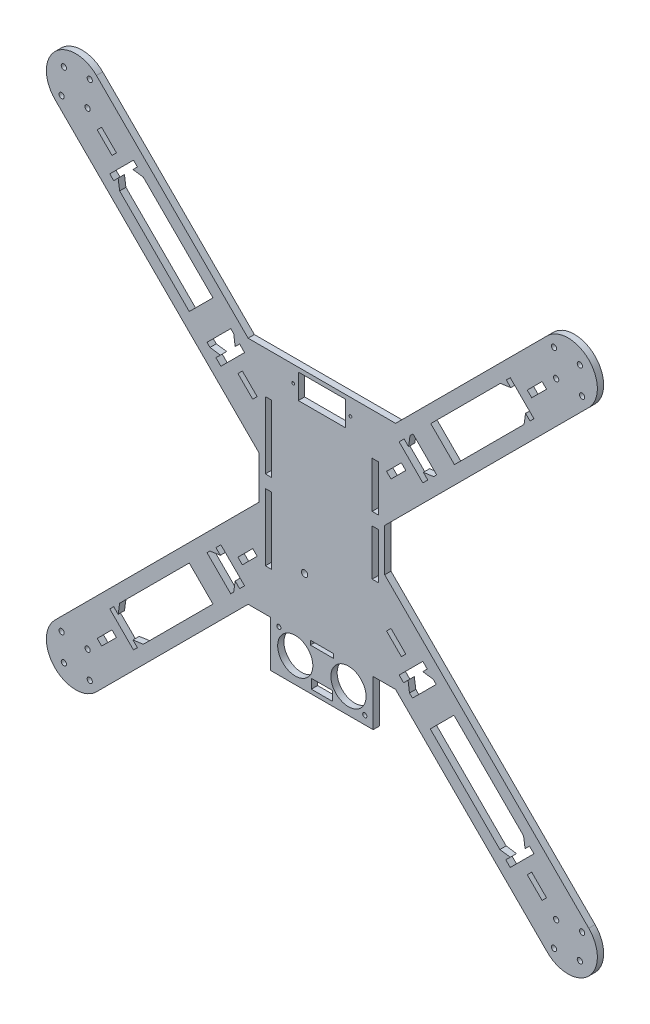
SolidWorks part; units mm, degrees
material "Custom Plastic"
ref_plane "Front Plane" through (0, 0, 0) normal (0, 0, 1) x (1, 0, 0)
ref_plane "Top Plane" through (0, 0, 0) normal (0, 1, 0) x (1, 0, 0)
ref_plane "Right Plane" through (0, 0, 0) normal (1, 0, 0) x (0, 0, -1)
sketch "Sketch1" plane through (0, 0, 0) normal (0, 0, 1) x (1, 0, 0)
  line L0 (117.5, 117.5) -> (-117.5, 117.5) construction
  line L1 (-117.5, 117.5) -> (117.5, -117.5) construction
  line L2 (117.5, -117.5) -> (-117.5, -117.5) construction
  line L3 (-117.5, -117.5) -> (117.5, 117.5) construction
  line L4 (117.5, 117.5) -> (117.5, -117.5) construction
  line L5 (-117.5, 117.5) -> (-117.5, -117.5) construction
  line L6 (0, 117.5) -> (0, -117.5) construction
  line L7 (35.201, 55) -> (-35.201, 55)
  line L8 (-30, 55) -> (30, 55) construction
  line L9 (-35.201, 55) -> (-107.6005, 127.3995)
  line L10 (-127.3995, 107.6005) -> (-30, 10.201)
  line L11 (-117.5, 0) -> (117.5, 0) construction
  line L12 (-30, 10.201) -> (-30, -10.201)
  line L13 (30, 55) -> (30, -55) construction
  line L14 (30, -55) -> (-30, -55) construction
  line L15 (-30, -55) -> (-30, 55) construction
  line L16 (30, 55) -> (-30, -55) construction
  line L17 (-24.5, -55) -> (-24.5, -77)
  line L18 (-127.3995, -107.6005) -> (-30, -10.201)
  line L19 (-24.5, -77) -> (24.5, -77)
  line L20 (-35.201, -55) -> (-107.6005, -127.3995)
  line L21 (35.201, -55) -> (24.5, -55)
  line L22 (35.201, -55) -> (107.6005, -127.3995)
  line L23 (127.3995, -107.6005) -> (30, -10.201)
  line L24 (30, 10.201) -> (30, -10.201)
  line L25 (127.3995, 107.6005) -> (30, 10.201)
  line L26 (35.201, 55) -> (107.6005, 127.3995)
  line L27 (24.5, -55) -> (24.5, -77)
  line L28 (-24.5, -55) -> (-35.201, -55)
  arc A0 (-107.6005, 127.3995) -> (-127.3995, 107.6005) centre (-117.5, 117.5) ccw
  arc A12 (-107.6005, -127.3995) -> (-127.3995, -107.6005) centre (-117.5, -117.5) cw
  arc A16 (107.6005, -127.3995) -> (127.3995, -107.6005) centre (117.5, -117.5) ccw
  arc A24 (107.6005, 127.3995) -> (127.3995, 107.6005) centre (117.5, 117.5) cw
  point P3 (0, 0)
  point P18 (0, 0)
  point P21 (0, -77)
  point P33 (-117.5, 117.5)
  point P34 (-30, 0)
  point P65 (0, -55)
  point P80 (0, 55)
  dimension "D3" = 14
  dimension "D8" = 24.5
  dimension "D7" = 22
  dimension "D1" = 235
  dimension "D2" = 235
  dimension "D4" = 60
  dimension "D5" = 110
  dimension "D6" = 28
extrude "Boss-Extrude1" add sketch "Sketch1" against normal blind 3
sketch "Sketch4" plane through (0, 0, 0) normal (0, 0, 1) x (1, 0, 0)
  line L0 (0, 0) -> (0, 55) construction
  line L1 (35.201, 55) -> (-35.201, 55) construction
  line L2 (0, 0) -> (-30, 0) construction
  line L3 (-30, 10.201) -> (-30, -10.201) construction
  line L4 (-30, 0) -> (-30, 10.201) construction
  line L5 (-30, 10.201) -> (-127.3995, 107.6005) construction
  line L6 (-35.201, 55) -> (-107.6005, 127.3995) construction
  line L7 (-107.6005, 127.3995) -> (-127.3995, 107.6005) construction
  line L8 (-110.7825, 124.2175) -> (-124.2175, 110.7825) construction
  line L9 (-123.1569, 123.1569) -> (-111.8431, 111.8431) construction
  circle A20 centre (-110.7825, 124.2175) radius 1.25
  circle A21 centre (-124.2175, 110.7825) radius 1.25
  circle A22 centre (-123.1569, 123.1569) radius 1.25
  circle A23 centre (-111.8431, 111.8431) radius 1.25
  circle A24 centre (111.8431, 111.8431) radius 1.25
  circle A25 centre (110.7825, 124.2175) radius 1.25
  circle A26 centre (123.1569, 123.1569) radius 1.25
  circle A27 centre (124.2175, 110.7825) radius 1.25
  circle A28 centre (111.8431, -111.8431) radius 1.25
  circle A29 centre (124.2175, -110.7825) radius 1.25
  circle A30 centre (123.1569, -123.1569) radius 1.25
  circle A31 centre (110.7825, -124.2175) radius 1.25
  circle A32 centre (-111.8431, -111.8431) radius 1.25
  circle A33 centre (-110.7825, -124.2175) radius 1.25
  circle A34 centre (-123.1569, -123.1569) radius 1.25
  circle A35 centre (-124.2175, -110.7825) radius 1.25
  point P16 (-117.5, 117.5)
  point P19 (-117.5, 117.5)
  point P26 (-117.5, 117.5)
  point P62 (0, 0)
  dimension "D4" = 2.5
  dimension "D2" = 19
  dimension "D3" = 16
extrude "Cut-Extrude1" cut sketch "Sketch4" against normal blind 3
sketch "Sketch5" plane through (0, 0, 0) normal (0, 0, 1) x (1, 0, 0)
  line L7 (-11.25, 53) -> (-11.25, 41.2)
  line L8 (-11.25, 41.2) -> (11.25, 41.2)
  line L9 (11.25, 41.2) -> (11.25, 53)
  line L10 (11.25, 53) -> (-11.25, 53)
  line L12 (0, 53) -> (0, 41.2) construction
  line L13 (-13.65, 47.1) -> (13.65, 47.1) construction
  line L14 (35.201, 55) -> (-35.201, 55) construction
  circle A2 centre (-13.65, 47.1) radius 0.65
  circle A3 centre (13.65, 47.1) radius 0.65
  point P20 (0, 47.1)
  point P21 (0, 47.1)
  point P26 (0, 55)
  dimension "D8" = 1.3
  dimension "D9" = 1.3
  dimension "D10" = 27.3
  dimension "D11" = 22.5
  dimension "D12" = 11.8
  dimension "D13" = 2
extrude "Cut-Extrude2" cut sketch "Sketch5" against normal blind 3
sketch "Sketch6" plane through (0, 0, 0) normal (0, 0, 1) x (1, 0, 0)
  line L1 (-11.25, 41.2) -> (11.25, 41.2) construction
  circle A0 centre (-8.25, -28.8) radius 1.5
  dimension "D3" = 3
  dimension "D1" = 70
  dimension "D2" = 3
extrude "Cut-Extrude3" cut sketch "Sketch6" against normal blind 3
sketch "Sketch7" plane through (0, 0, 0) normal (0, 0, 1) x (1, 0, 0)
  line L0 (-22.5, -55) -> (-22.5, -75) construction
  line L5 (-22.5, -75) -> (22.5, -75) construction
  line L6 (22.5, -75) -> (22.5, -55) construction
  line L7 (22.5, -55) -> (-22.5, -55) construction
  line L8 (0, -55) -> (0, -75) construction
  line L9 (-12.7, -65) -> (0, -65) construction
  line L10 (-24.5, -77) -> (24.5, -77) construction
  line L11 (-24.5, -55) -> (-24.5, -77) construction
  line L12 (-5.5, -55) -> (-5.5, -57)
  line L13 (-5.5, -57) -> (5.5, -57)
  line L15 (5.5, -55) -> (-5.5, -55)
  line L16 (-5, -75) -> (-5, -70.5)
  line L17 (-5, -70.5) -> (5, -70.5)
  line L21 (5, -75) -> (-5, -75)
  line L22 (5.5, -55) -> (5.5, -57)
  line L23 (5, -75) -> (5, -70.5)
  circle A5 centre (-20.5, -57) radius 1
  circle A6 centre (-12.7, -65) radius 8.4
  circle A7 centre (12.7, -65) radius 8.4
  circle A8 centre (20.5, -73) radius 1
  point P25 (0, -57)
  point P26 (0, -70.5)
  dimension "D3" = 2
  dimension "D6" = 20
  dimension "D13" = 5
  dimension "D5" = 45
  dimension "D1" = 2
  dimension "D4" = 16.8
  dimension "D14" = 2
  dimension "D2" = 2
  dimension "D7" = 2
  dimension "D8" = 2
  dimension "D9" = 12.7
  dimension "D10" = 5.5
  dimension "D11" = 2
  dimension "D12" = 4.5
  dimension "D15" = 2
  dimension "D16" = 2
extrude "Cut-Extrude4" cut sketch "Sketch7" against normal blind 3
sketch "Sketch8" plane through (0, 0, 0) normal (0, 0, 1) x (1, 0, 0)
  line L0 (101.2365, -89.9228) -> (89.9228, -101.2365)
  line L1 (89.9228, -101.2365) -> (87.8015, -99.1152)
  line L2 (36.8898, -48.2035) -> (48.2035, -36.8898)
  line L3 (48.2035, -36.8898) -> (50.3249, -39.0111)
  line L4 (105.4792, -85.6802) -> (85.6802, -105.4792) construction
  line L5 (127.3995, -107.6005) -> (30, -10.201) construction
  line L6 (35.201, -55) -> (107.6005, -127.3995) construction
  line L7 (40.0718, -37.9505) -> (37.9505, -40.0718)
  line L8 (115.8431, -107.8431) -> (111.8431, -111.8431) construction
  line L9 (37.9505, -40.0718) -> (30.8794, -33.0007)
  line L10 (50.5675, 39.2538) -> (48.2035, 36.8898)
  line L11 (30.8794, -33.0007) -> (33.0007, -30.8794)
  line L12 (33.0007, -30.8794) -> (40.0718, -37.9505)
  line L13 (42.5467, -42.5467) -> (39.0111, -39.0111) construction
  line L14 (35.201, -55) -> (107.6005, -127.3995) construction
  line L15 (100.1759, -98.0546) -> (98.0546, -100.1759)
  line L16 (98.0546, -100.1759) -> (105.1256, -107.247)
  line L17 (105.1256, -107.247) -> (107.247, -105.1256)
  line L18 (107.247, -105.1256) -> (100.1759, -98.0546)
  line L19 (99.1152, -99.1152) -> (95.5797, -95.5797) construction
  line L20 (-101.2365, -89.9228) -> (-99.3579, -88.0442)
  line L21 (-100.1759, -98.0546) -> (-107.247, -105.1256)
  line L22 (-107.247, -105.1256) -> (-105.1256, -107.247)
  line L23 (-105.1256, -107.247) -> (-98.0546, -100.1759)
  line L24 (-98.0546, -100.1759) -> (-100.1759, -98.0546)
  line L25 (-89.9228, -101.2365) -> (-101.2365, -89.9228)
  line L26 (-36.8898, -48.2035) -> (-39.2538, -50.5675)
  line L27 (-48.2035, -36.8898) -> (-36.8898, -48.2035)
  line L28 (-37.9505, -40.0718) -> (-40.0718, -37.9505)
  line L29 (-30.8794, -33.0007) -> (-37.9505, -40.0718)
  line L30 (-40.0718, -37.9505) -> (-33.0007, -30.8794)
  line L31 (-33.0007, -30.8794) -> (-30.8794, -33.0007)
  line L32 (-89.9228, 101.2365) -> (-88.0442, 99.3579)
  line L33 (-98.0546, 100.1759) -> (-105.1256, 107.247)
  line L34 (-105.1256, 107.247) -> (-107.247, 105.1256)
  line L35 (-107.247, 105.1256) -> (-100.1759, 98.0546)
  line L36 (-100.1759, 98.0546) -> (-98.0546, 100.1759)
  line L37 (-101.2365, 89.9228) -> (-89.9228, 101.2365)
  line L38 (-48.2035, 36.8898) -> (-50.5675, 39.2538)
  line L39 (-36.8898, 48.2035) -> (-48.2035, 36.8898)
  line L40 (-40.0718, 37.9505) -> (-37.9505, 40.0718)
  line L41 (-33.0007, 30.8794) -> (-40.0718, 37.9505)
  line L42 (-37.9505, 40.0718) -> (-30.8794, 33.0007)
  line L43 (-30.8794, 33.0007) -> (-33.0007, 30.8794)
  line L44 (101.2365, 89.9228) -> (99.3579, 88.0442)
  line L45 (100.1759, 98.0546) -> (107.247, 105.1256)
  line L46 (107.247, 105.1256) -> (105.1256, 107.247)
  line L47 (105.1256, 107.247) -> (98.0546, 100.1759)
  line L48 (98.0546, 100.1759) -> (100.1759, 98.0546)
  line L49 (89.9228, 101.2365) -> (101.2365, 89.9228)
  line L50 (36.8898, 48.2035) -> (39.2538, 50.5675)
  line L51 (48.2035, 36.8898) -> (36.8898, 48.2035)
  line L52 (37.9505, 40.0718) -> (40.0718, 37.9505)
  line L53 (30.8794, 33.0007) -> (37.9505, 40.0718)
  line L54 (40.0718, 37.9505) -> (33.0007, 30.8794)
  line L55 (33.0007, 30.8794) -> (30.8794, 33.0007)
  line L56 (30, 10.201) -> (127.3995, 107.6005) construction
  line L57 (42.0822, 53.3959) -> (85.2157, 96.5294)
  line L58 (96.5294, 85.2157) -> (53.3959, 42.0822)
  line L59 (88.0442, 99.3579) -> (89.9228, 101.2365)
  line L60 (99.1152, -87.8015) -> (96.9939, -89.9228)
  line L61 (-96.5294, -85.2157) -> (-53.3959, -42.0822)
  line L62 (96.9939, -89.9228) -> (96.2868, -84.9731)
  line L63 (99.1152, -87.8015) -> (101.2365, -89.9228)
  line L64 (87.8015, -99.1152) -> (89.9228, -96.9939)
  line L65 (-88.0442, -99.3579) -> (-89.9228, -101.2365)
  line L66 (89.9228, -96.9939) -> (84.9731, -96.2868)
  line L67 (84.9731, -96.2868) -> (41.8396, -53.1533)
  line L68 (50.3249, -39.0111) -> (48.2035, -41.1325)
  line L69 (48.2035, -41.1325) -> (53.1533, -41.8396)
  line L70 (53.1533, -41.8396) -> (96.2868, -84.9731)
  line L71 (39.0111, -50.3249) -> (41.1325, -48.2035)
  line L72 (41.1325, -48.2035) -> (41.8396, -53.1533)
  line L73 (39.0111, -50.3249) -> (36.8898, -48.2035)
  line L74 (-90.1655, -97.2365) -> (-85.2157, -96.5294)
  line L75 (-88.0442, -99.3579) -> (-90.1655, -97.2365)
  line L76 (-97.2365, -90.1655) -> (-96.5294, -85.2157)
  line L77 (-99.3579, -88.0442) -> (-97.2365, -90.1655)
  line L78 (-41.3751, -48.4462) -> (-42.0822, -53.3959)
  line L79 (-39.2538, -50.5675) -> (-41.3751, -48.4462)
  line L80 (-48.4462, -41.3751) -> (-53.3959, -42.0822)
  line L81 (-50.5675, -39.2538) -> (-48.4462, -41.3751)
  line L82 (-97.2365, 90.1655) -> (-96.5294, 85.2157)
  line L83 (-99.3579, 88.0442) -> (-97.2365, 90.1655)
  line L84 (-90.1655, 97.2365) -> (-85.2157, 96.5294)
  line L85 (-88.0442, 99.3579) -> (-90.1655, 97.2365)
  line L86 (-48.4462, 41.3751) -> (-53.3959, 42.0822)
  line L87 (-50.5675, 39.2538) -> (-48.4462, 41.3751)
  line L88 (-41.3751, 48.4462) -> (-42.0822, 53.3959)
  line L89 (-39.2538, 50.5675) -> (-41.3751, 48.4462)
  line L90 (90.1655, 97.2365) -> (85.2157, 96.5294)
  line L91 (88.0442, 99.3579) -> (90.1655, 97.2365)
  line L92 (97.2365, 90.1655) -> (96.5294, 85.2157)
  line L93 (99.3579, 88.0442) -> (97.2365, 90.1655)
  line L94 (41.3751, 48.4462) -> (42.0822, 53.3959)
  line L95 (39.2538, 50.5675) -> (41.3751, 48.4462)
  line L96 (48.4462, 41.3751) -> (53.3959, 42.0822)
  line L97 (50.5675, 39.2538) -> (48.4462, 41.3751)
  line L98 (-39.2538, 50.5675) -> (-36.8898, 48.2035)
  line L99 (-53.3959, 42.0822) -> (-96.5294, 85.2157)
  line L100 (-99.3579, 88.0442) -> (-101.2365, 89.9228)
  line L101 (-85.2157, 96.5294) -> (-42.0822, 53.3959)
  line L102 (-42.0822, -53.3959) -> (-85.2157, -96.5294)
  line L103 (-50.5675, -39.2538) -> (-48.2035, -36.8898)
  point P10 (95.5797, -95.5797)
  point P11 (95.5797, -95.5797)
  point P68 (0, 0)
  point P122 (0, 0)
  dimension "D1" = 23
  dimension "D2" = 75
  dimension "D3" = 3
  dimension "D4" = 10
  dimension "D5" = 5
  dimension "D6" = 6
  dimension "D7" = 3
  dimension "D8" = 10
  dimension "D9" = 5
  dimension "D11" = 6
  dimension "D12" = 3
  dimension "D13" = 4
  dimension "D14" = 3
  dimension "D15" = 3
  dimension "D16" = 4
  dimension "D17" = 3
  dimension "D18" = 3
  dimension "D19" = 4
  dimension "D20" = 3
  dimension "D21" = 3
  dimension "D22" = 4
  dimension "D23" = 3
  dimension "D10" = 4
extrude "Cut-Extrude5" cut sketch "Sketch8" against normal through all
sketch "Sketch9" plane through (-5.6569, 5.6569, 0) normal (0.7071, -0.7071, 0) x (0, 0, -1)
  line L0 (3, 128.5132) -> (3, 67.5132) construction
  line L1 (3, 81.5132) -> (0, 81.5132)
  line L2 (3, 81.5132) -> (3, 69.5132)
  line L3 (3, 69.5132) -> (0, 69.5132)
  line L4 (0, 81.5132) -> (0, 69.5132)
  line L5 (0, 128.5132) -> (0, 67.5132) construction
  line L6 (0, 0) -> (28.0274, 0) construction
  line L7 (3, 63.5132) -> (0, 63.5132) construction
  dimension "D1" = 6
  dimension "D2" = 12
extrude "Boss-Extrude2" add sketch "Sketch9" along normal up to next
sketch "Sketch11" plane through (5.6569, 5.6569, 0) normal (-0.7071, -0.7071, 0) x (0, 0, 1)
  line L0 (-3, -128.1701) -> (-3, -67.1701) construction
  line L1 (-3, -69.1701) -> (0, -69.1701)
  line L2 (-3, -69.1701) -> (-3, -81.1701)
  line L3 (-3, -81.1701) -> (0, -81.1701)
  line L4 (0, -69.1701) -> (0, -81.1701)
  line L5 (0, -128.1701) -> (0, -67.1701) construction
  line L6 (-3, -63.1701) -> (0, -63.1701) construction
  dimension "D1" = 6
  dimension "D2" = 12
extrude "Boss-Extrude3" add sketch "Sketch11" along normal up to next
sketch "Sketch12" plane through (5.6569, -5.6569, 0) normal (-0.7071, 0.7071, 0) x (0, 0, 1)
  line L0 (-3, -128.5132) -> (-3, -67.5132) construction
  line L1 (-3, -69.5132) -> (0, -69.5132)
  line L2 (-3, -69.5132) -> (-3, -81.5132)
  line L3 (-3, -81.5132) -> (0, -81.5132)
  line L4 (0, -69.5132) -> (0, -81.5132)
  line L5 (0, -128.5132) -> (0, -67.5132) construction
  dimension "D1" = 6
  dimension "D2" = 12
extrude "Boss-Extrude4" add sketch "Sketch12" along normal up to next
sketch "Sketch13" plane through (5.6569, 5.6569, 0) normal (-0.7071, -0.7071, 0) x (0, 0, 1)
  line L0 (-3, 67.5132) -> (-3, 128.5132) construction
  line L1 (-3, 69.5132) -> (0, 69.5132)
  line L2 (-3, 69.5132) -> (-3, 81.5132)
  line L3 (-3, 81.5132) -> (0, 81.5132)
  line L4 (0, 69.5132) -> (0, 81.5132)
  line L5 (0, 67.5132) -> (0, 128.5132) construction
  dimension "D1" = 6
  dimension "D2" = 12
extrude "Boss-Extrude5" add sketch "Sketch13" along normal up to next
sketch "Sketch14" plane through (0, 0, -3) normal (0, 0, -1) x (-1, 0, 0)
  line L0 (30, 0) -> (-30, 0) construction
  line L1 (30, 10.201) -> (30, -10.201) construction
  line L2 (-30, -10.201) -> (-30, 10.201) construction
  line L3 (25.5, -3) -> (25.5, 3) construction
  line L4 (27, -3) -> (24, -3)
  line L5 (27, -3) -> (27, -35)
  line L6 (27, -35) -> (24, -35)
  line L7 (24, -3) -> (24, -35)
  line L8 (27, 3) -> (24, 3)
  line L9 (27, 3) -> (27, 35)
  line L10 (27, 35) -> (24, 35)
  line L11 (24, 3) -> (24, 35)
  line L12 (24, -35) -> (-25.5, -35) construction
  line L13 (-25.5, -35) -> (-25.5, -15) construction
  line L15 (-24, -15) -> (-27, -15)
  line L16 (-24, -15) -> (-24, 7)
  line L17 (-24, 7) -> (-27, 7)
  line L18 (-27, -15) -> (-27, 7)
  line L19 (-24, 13) -> (-27, 13)
  line L20 (-24, 13) -> (-24, 35)
  line L21 (-24, 35) -> (-27, 35)
  line L22 (-27, 13) -> (-27, 35)
  point P16 (25.5, 0)
  point P23 (-25.5, -15)
  point P28 (-25.5, 13)
  dimension "D1" = 6
  dimension "D2" = 32
  dimension "D3" = 3
  dimension "D4" = 3
  dimension "D5" = 20
  dimension "D6" = 4.5
  dimension "D7" = 6
  dimension "D8" = 22
  dimension "D9" = 3
extrude "Cut-Extrude6" cut sketch "Sketch14" against normal through all
